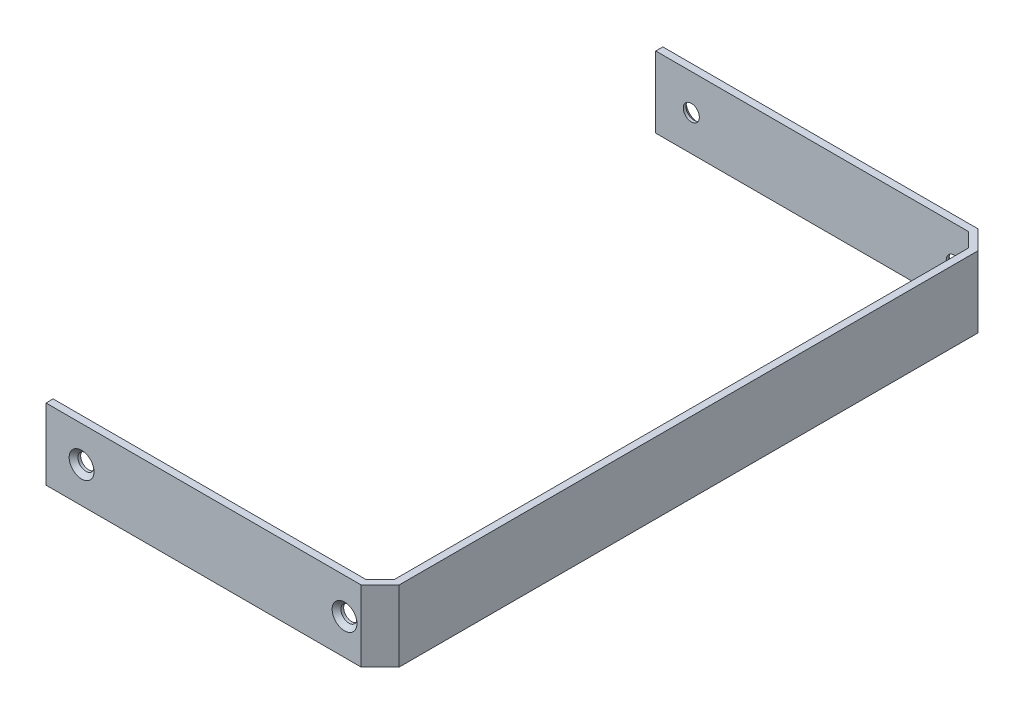
SolidWorks part; units mm, degrees
ref_plane "Front Plane" through (0, 0, 0) normal (0, 0, 1) x (1, 0, 0)
ref_plane "Top Plane" through (0, 0, 0) normal (0, 1, 0) x (1, 0, 0)
ref_plane "Right Plane" through (0, 0, 0) normal (1, 0, 0) x (0, 0, -1)
sketch "Sketch3" plane through (0, 0, 0) normal (0, 0, 1) x (1, 0, 0)
  line L1 (44.7153, 9.525) -> (-44.7153, 9.525)
  line L2 (44.7153, 9.525) -> (44.7153, -9.525)
  line L3 (44.7153, -9.525) -> (-44.7153, -9.525)
  line L4 (-44.7153, 9.525) -> (-44.7153, -9.525)
  point P1 (44.7153, 0)
  point P4 (0, 9.525)
  dimension "D1" = 89.4307
  dimension "D2" = 19.05
extrude "Boss-Extrude1" add sketch "Sketch3" along normal mid plane 165.0767
sketch "Sketch4" plane through (0, -9.525, 0) normal (0, -1, 0) x (1, 0, 0)
  line L1 (-44.7153, 80.6333) -> (42.8103, 80.6333)
  line L2 (-44.7153, 80.6333) -> (-44.7153, -80.6333)
  line L3 (-44.7153, -80.6333) -> (42.8103, -80.6333)
  line L4 (42.8103, 80.6333) -> (42.8103, -80.6333)
  line L5 (-44.7153, 82.5383) -> (44.7153, 82.5383) construction
  line L6 (44.7153, 82.5383) -> (44.7153, -82.5383) construction
  line L7 (-44.7153, 82.5383) -> (-44.7153, -82.5383) construction
  point P6 (42.8103, 0)
  dimension "D1" = 1.905
  dimension "D2" = 1.905
extrude "Cut-Extrude1" cut sketch "Sketch4" against normal through all
sketch "Sketch5" plane through (0, 0, -82.5383) normal (0, 0, -1) x (-1, 0, 0)
  line L2 (35.1903, 0) -> (35.1903, -9.525) construction
  line L3 (44.7153, -9.525) -> (-44.7153, -9.525) construction
  line L13 (-35.1903, 0) -> (-35.1903, -9.525) construction
  line L15 (-35.1903, 0) -> (-44.7153, 0) construction
  line L17 (-44.7153, -9.525) -> (-44.7153, 9.525) construction
  line L18 (35.1903, 0) -> (44.7153, 0) construction
  line L19 (44.7153, 9.525) -> (44.7153, -9.525) construction
  point P9 (35.1903, 0)
  point P48 (-35.1903, 0)
hole_wizard "#6 Clearance Hole1" positions "Sketch5" profile "Sketch6" hole size "#6" standard "ANSI Inch" end condition up to next
sketch "Sketch6" plane through (35.1903, 0, -82.5383) normal (1, 0, 0) x (0, 1, 0)
  line L0 (0, 0) -> (0, 1.905)
  line L1 (0, 1.905) -> (2.1526, 1.905)
  line L2 (2.1526, 1.905) -> (2.1526, 1.1747)
  line L3 (2.1526, 1.1747) -> (3.3274, 0)
  line L5 (3.3274, 0) -> (0, 0)
  line L6 (-2.1526, 1.1747) -> (-3.3274, 0) construction
  line L11 (0, -6.35) -> (0, 107.95) construction
  dimension "Thru Hole Dia." = 4.3053
  dimension "Thru Hole Depth" = 1.905
  dimension "Near C'Sink Dia." = 6.6548
  dimension "Near C'Sink Angle" = 90
sketch "Sketch7" plane through (0, 0, 82.5383) normal (0, 0, 1) x (1, 0, 0)
  circle A0 centre (35.1903, 0) radius 2.1526 construction
  circle A1 centre (-35.1903, 0) radius 2.1526 construction
  point P0 (-35.1903, 0)
  point P1 (35.1903, 0)
hole_wizard "#6 Clearance Hole2" positions "Sketch7" profile "Sketch8" hole size "#6" standard "ANSI Inch"
sketch "Sketch8" plane through (-35.1903, 0, 82.5383) normal (1, 0, 0) x (0, -1, 0)
  line L0 (0, 0) -> (0, 8.1514)
  line L1 (0, 8.1514) -> (2.1526, 6.858)
  line L2 (2.1526, 6.858) -> (2.1526, 1.1748)
  line L3 (2.1526, 1.1748) -> (3.3274, 0)
  line L5 (3.3274, 0) -> (0, 0)
  line L6 (-2.1526, 1.1747) -> (-3.3274, 0) construction
  line L10 (0, 8.1514) -> (-2.1527, 6.858) construction
  line L11 (0, -6.35) -> (0, 107.95) construction
  dimension "Hole Dia." = 4.3053
  dimension "Hole Depth" = 6.858
  dimension "Near C'Sink Dia." = 6.6548
  dimension "Near C'Sink Angle" = 90
  dimension "Drill Angle" = 118
chamfer "Chamfer1" distance 3.81 angle 45 2 edges at (42.8103, 0, 80.6333) (42.8103, 0, -80.6333)
chamfer "Chamfer2" distance 5.08 angle 45 2 edges at (44.7153, 0, -82.5383) (44.7153, 0, 82.5383)
